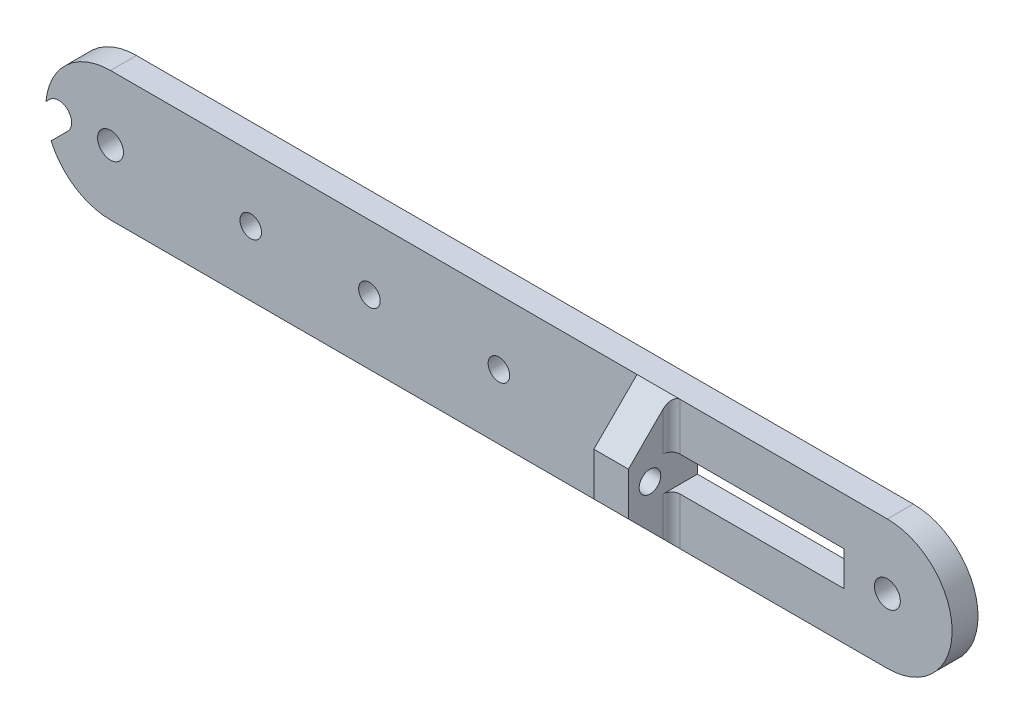
SolidWorks part; units mm, degrees
ref_plane "Plan de face" through (0, 0, 0) normal (0, 0, 1) x (1, 0, 0)
ref_plane "Plan de dessus" through (0, 0, 0) normal (0, 1, 0) x (1, 0, 0)
ref_plane "Plan de droite" through (0, 0, 0) normal (1, 0, 0) x (0, 0, -1)
sketch "Esquisse1" plane through (0, 0, 0) normal (0, 0, 1) x (1, 0, 0)
  line L0 (-74.3787, 0) -> (69.7437, 0) construction
  line L1 (0, 0) -> (0, 19.0596) construction
  line L2 (90, -15) -> (-90, -15)
  line L3 (90, 15) -> (-90, 15)
  line L5 (40, -4) -> (80, -4)
  line L6 (40, -4) -> (40, 4)
  line L7 (40, 4) -> (80, 4)
  line L8 (80, -4) -> (80, 4)
  line L9 (40, -4) -> (80, 4) construction
  line L10 (40, 4) -> (80, -4) construction
  arc A0 (90, -15) -> (90, 15) centre (90, 0) ccw
  circle A1 centre (90, 0) radius 3
  circle A2 centre (-90, 0) radius 3
  arc A3 (-90, -15) -> (-90, 15) centre (-90, 0) cw
  circle A4 centre (0, 0) radius 2.5
  circle A5 centre (-57.5, 0) radius 2.5
  circle A6 centre (-30, 0) radius 2.5
  point P4 (60, 0)
  point P17 (0, -15)
  point P20 (0, 15)
  dimension "D1" = 30
  dimension "D3" = 6
  dimension "D7" = 5
  dimension "D8" = 5
  dimension "D9" = 5
  dimension "D2" = 90
  dimension "D4" = 8
  dimension "D5" = 40
  dimension "D6" = 60
  dimension "D10" = 30
  dimension "D11" = 30
extrude "Boss.-Extru.1" add sketch "Esquisse1" along normal blind 6
sketch "Esquisse2" plane through (40, 0, 0) normal (1, 0, 0) x (0, 0, -1)
  line L0 (0, -4) -> (-6, 4) construction
  line L1 (-6, 4) -> (-6, 0) construction
  line L2 (-6, 4) -> (-6, -4) construction
  line L3 (-6, 0) -> (-15.5036, 0) construction
  line L4 (-6, 15) -> (-6, -15) construction
  line L6 (-16, 5) -> (-16, -5)
  line L8 (-6, 5) -> (-6, -5)
  line L9 (-16, 5) -> (-6, -5) construction
  line L10 (-16, -5) -> (-6, 5) construction
  line L11 (-6, -15) -> (-16, -5)
  line L12 (-6, -15) -> (-6, -5)
  line L13 (-6, 5) -> (-6, 15)
  line L14 (-6, 15) -> (-16, 5)
  circle A0 centre (-11, 0) radius 2.5
  point P7 (-11, 0)
  dimension "D3" = 5
  dimension "D1" = 10
  dimension "D2" = 10
extrude "Boss.-Extru.2" add sketch "Esquisse2" against normal blind 8
fillet "Congé2" radius 2 2 edges
sketch "Esquisse3" plane through (32, 0, 0) normal (-1, 0, 0) x (0, 0, 1)
  line L0 (11, 0) -> (11, 4) construction
  line L1 (11, 0) -> (14.4641, 2) construction
  line L2 (11, 0) -> (14.4641, -2) construction
  line L3 (11, 4) -> (14.4641, 2)
  line L4 (14.4641, 2) -> (14.4641, -2)
  line L5 (14.4641, -2) -> (11, -4)
  line L6 (7.5359, 2) -> (7.5359, -2)
  line L7 (11, 4) -> (7.5359, 2)
  line L8 (7.5359, -2) -> (11, -4)
  dimension "D2" = 60
  dimension "D3" = 60
extrude "Enlèv. mat.-Extru.1" cut sketch "Esquisse3" against normal blind 4
sketch "Esquisse4" plane through (0, 0, 6) normal (0, 0, 1) x (1, 0, 0)
  line L0 (-90, 0) -> (-105, 0) construction
  line L1 (-105, 0) -> (-102, 0) construction
  line L2 (-102, 0) -> (-99.8787, -2.1213) construction
  line L3 (-99.8787, -2.1213) -> (-104.1213, 2.1213)
  line L4 (-99.8787, -2.1213) -> (-104.1213, 2.1213)
  line L5 (-99.8787, -2.1213) -> (-104.2614, -6.504)
  line L6 (-104.1213, 2.1213) -> (-108.504, -2.2614)
  line L7 (-104.2614, -6.504) -> (-108.504, -2.2614)
  arc A0 (-90, 15) -> (-90, -15) centre (-90, 0) ccw construction
  circle A1 centre (-102, 0) radius 3
  arc M9 (-90, 15) -> (-90, -15) centre (-90, 0) ccw
  dimension "D1" = 3
  dimension "D2" = 135
extrude "Enlèv. mat.-Extru.4" cut sketch "Esquisse4" against normal blind 10 contours L3 A1 | A1 L6 M9 | A1 L5 M9 | L3 A1 region at (-102.9003, -0.9003, 6) region at (-101.0997, 0.9003, 6) region at (-103.2777, -3.6386, 6) region at (-104.7977, 1.1965, 6)
